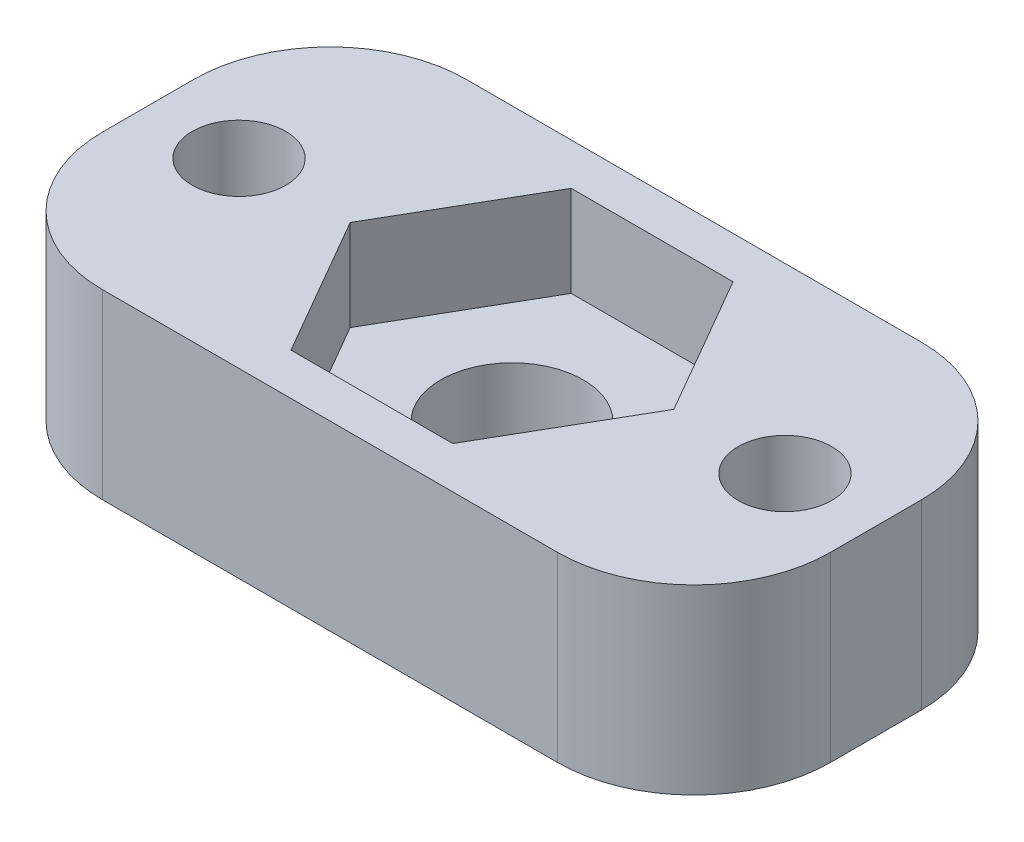
SolidWorks part; units mm, degrees
ref_plane "Front Plane" through (0, 0, 0) normal (0, 0, 1) x (1, 0, 0)
ref_plane "Top Plane" through (0, 0, 0) normal (0, 1, 0) x (1, 0, 0)
ref_plane "Right Plane" through (0, 0, 0) normal (1, 0, 0) x (0, 0, -1)
sketch "Sketch1" plane through (0, 0, 0) normal (0, 1, 0) x (1, 0, 0)
  line L0 (0, 0) -> (0, 6.35) construction
  line L1 (5.6459, 0) -> (2.823, 4.8895)
  line L2 (2.823, 4.8895) -> (-2.823, 4.8895)
  line L3 (-2.823, 4.8895) -> (-5.6459, 0)
  line L4 (-5.6459, 0) -> (-2.823, -4.8895)
  line L5 (-2.823, -4.8895) -> (2.823, -4.8895)
  line L6 (2.823, -4.8895) -> (5.6459, 0)
  line L7 (-12.7, 6.35) -> (12.7, 6.35)
  line L8 (-12.7, 6.35) -> (-12.7, -6.35)
  line L9 (-12.7, -6.35) -> (12.7, -6.35)
  line L10 (12.7, 6.35) -> (12.7, -6.35)
  line L11 (-12.7, 6.35) -> (12.7, -6.35) construction
  line L12 (-12.7, -6.35) -> (12.7, 6.35) construction
  line L14 (12.7, 0) -> (0, 0) construction
  circle A0 centre (0, 0) radius 4.8895 construction
  circle A1 centre (0, 0) radius 2.4892
  circle A2 centre (9.525, 0) radius 1.632
  circle A3 centre (-9.525, 0) radius 1.632
  dimension "D1" = 4.9784
  dimension "D2" = 9.779
  dimension "D5" = 3.2639
  dimension "D6" = 19.05
  dimension "D3" = 25.4
  dimension "D4" = 12.7
extrude "Boss-Extrude1" add sketch "Sketch1" along normal blind 3.175 contours L10 L7 L8 L9 L6 L5 L4 L3 L2 L1 A2 A3 | L5 L6 L1 L2 L3 L4 A1 region at (4.1051, 0, 2.3701) region at (0, 0, -6.066)
extrude "Boss-Extrude2" add sketch "Sketch1<3>" along normal offset from surface (6.35 mm away) 3.175 contours L10 L7 L8 L9 L6 L5 L4 L3 L2 L1 A2 A3 region at (0, 0, -6.066) up to face at (0, 3.175, 0) offset beyond the face yes
sketch "Sketch1<3>" plane through (0, 0, 0) normal (0, 1, 0) x (1, 0, 0) same geometry as "Sketch1"
fillet "Fillet1" radius 4.7625 4 edges at (12.7, 3.175, -6.35) (12.7, 3.175, 6.35) (-12.7, 3.175, -6.35) (-12.7, 3.175, 6.35)
